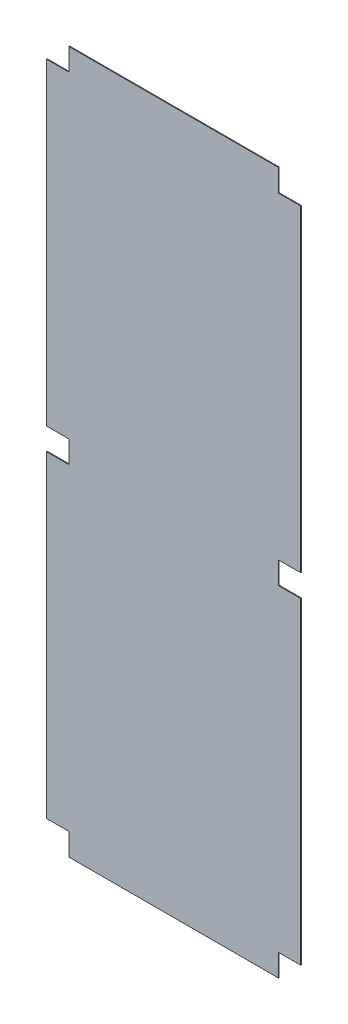
SolidWorks part; units mm, degrees
ref_plane "Front Plane" through (0, 0, 0) normal (0, 0, 1) x (1, 0, 0)
ref_plane "Top Plane" through (0, 0, 0) normal (0, 1, 0) x (1, 0, 0)
ref_plane "Right Plane" through (0, 0, 0) normal (1, 0, 0) x (0, 0, -1)
sketch "Sketch1" plane through (0, 0, 0) normal (0, 0, 1) x (1, 0, 0)
  line L1 (0, 0) -> (240, 0)
  line L2 (0, 0) -> (0, 663.4)
  line L3 (0, 663.4) -> (240, 663.4)
  line L4 (240, 0) -> (240, 663.4)
  dimension "D1" = 663.4
  dimension "D2" = 240
base flange "Base-Flange1" sketch "Sketch1" thickness 0.7 reverse thickness direction no parameters "D1"=0.7
sketch "Sketch2" plane through (0, 0, 0) normal (0, 0, 1) x (1, 0, 0)
  line L0 (120, 663.4) -> (120, 331.7) construction
  line L1 (240, 663.4) -> (219, 663.4)
  line L2 (240, 663.4) -> (240, 642.4)
  line L3 (240, 642.4) -> (219, 642.4)
  line L4 (219, 663.4) -> (219, 642.4)
  line L5 (240, 663.4) -> (0, 663.4) construction
  line L6 (120, 331.7) -> (240, 331.7) construction
  line L7 (240, 0) -> (240, 663.4) construction
  line L8 (21, 663.4) -> (21, 642.4)
  line L9 (0, 642.4) -> (21, 642.4)
  line L10 (0, 663.4) -> (0, 642.4)
  line L11 (0, 663.4) -> (21, 663.4)
  line L12 (0, 0) -> (21, 0)
  line L13 (0, 0) -> (0, 21)
  line L14 (0, 21) -> (21, 21)
  line L15 (21, 0) -> (21, 21)
  line L16 (219, 0) -> (219, 21)
  line L17 (240, 21) -> (219, 21)
  line L18 (240, 0) -> (240, 21)
  line L19 (240, 0) -> (219, 0)
  dimension "D1" = 21
  dimension "D2" = 21
extrude "Cut-Extrude1" cut sketch "Sketch2" against normal blind 10 normal cut yes
sketch "Sketch3" plane through (0, 0, -0.7) normal (0, 0, -1) x (-1, 0, 0)
  line L0 (0, 642.4) -> (0, 21) construction
  line L1 (0, 321.2) -> (-21, 321.2)
  line L2 (0, 321.2) -> (0, 342.2)
  line L3 (0, 342.2) -> (-21, 342.2)
  line L4 (-21, 321.2) -> (-21, 342.2)
  line L5 (-120, 663.4) -> (-120, 630.3113) construction
  line L6 (-219, 663.4) -> (-21, 663.4) construction
  line L7 (-219, 321.2) -> (-219, 342.2)
  line L8 (-240, 342.2) -> (-219, 342.2)
  line L9 (-240, 321.2) -> (-240, 342.2)
  line L10 (-240, 321.2) -> (-219, 321.2)
  point P6 (0, 331.7)
  point P7 (0, 331.7)
  dimension "D1" = 21
  dimension "D2" = 21
extrude "Cut-Extrude2" cut sketch "Sketch3" against normal blind 10 normal cut yes
sketch "Bend-Lines1" [suppressed] plane through (0, 0, 0) normal (0, 1, 0) x (1, 0, 0)
sketch "Bounding-Box1" [suppressed] plane through (0, 0, 0) normal (0, 1, 0) x (1, 0, 0)
sheet metal parameters "Sheet-Metal1" thickness 0.7 parameters "D1"=0.7
flat pattern "Flat-Pattern1" [suppressed]
sketch "Bend-Lines2" plane through (0, 0, 0) normal (0, 1, 0) x (1, 0, 0)
sketch3d "Bounding-Box2" [suppressed]
  line L0 (240, 819.4, 0) -> (240, 0, 0) construction
  line L1 (0, 819.4, 0) -> (0, 0, 0) construction
  line L2 (240, 819.4, 0) -> (0, 819.4, 0) construction
  line L3 (240, 0, 0) -> (0, 0, 0) construction
sheet metal parameters "Sheet-Metal2" thickness 0.7 parameters "D1"=0.7
flat pattern "Flat-Pattern1"
sketch "Bend-Lines2" plane through (0, 0, 0) normal (0, 1, 0) x (1, 0, 0)
sketch3d "Bounding-Box2" [suppressed]
  line L0 (240, 819.4, 0) -> (240, 0, 0) construction
  line L1 (0, 819.4, 0) -> (0, 0, 0) construction
  line L2 (240, 819.4, 0) -> (0, 819.4, 0) construction
  line L3 (240, 0, 0) -> (0, 0, 0) construction
sheet metal parameters "Sheet-Metal3" thickness 0.7 parameters "D1"=0.7
flat pattern "Flat-Pattern1"
sketch "Bend-Lines2" plane through (0, 0, 0) normal (0, 1, 0) x (1, 0, 0)
sketch3d "Bounding-Box2" [suppressed]
  line L0 (240, 663.4, 0) -> (240, 0, 0) construction
  line L1 (0, 663.4, 0) -> (0, 0, 0) construction
  line L2 (240, 663.4, 0) -> (0, 663.4, 0) construction
  line L3 (240, 0, 0) -> (0, 0, 0) construction
